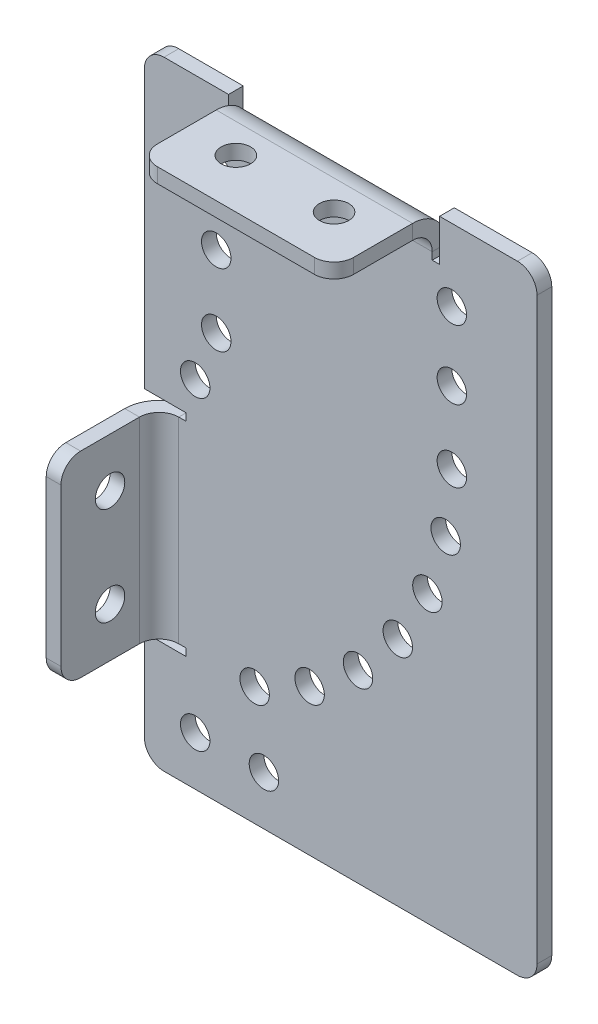
SolidWorks part; units mm, degrees
note: The reader was unsure of these and kept them because the rebuilt part matched: thickness of "基体-法兰2", "边线-法兰2", "边线-法兰3", "钣金10", "钣金11", "钣金12"; flange length of "边线-法兰2", "边线-法兰3".
ref_plane "前视基准面" through (0, 0, 0) normal (0, 0, 1) x (1, 0, 0)
ref_plane "上视基准面" through (0, 0, 0) normal (0, 1, 0) x (1, 0, 0)
ref_plane "右视基准面" through (0, 0, 0) normal (1, 0, 0) x (0, 0, -1)
other "Configuration Table"
sketch "草图1" plane through (0, 0, 0) normal (0, 0, 1) x (1, 0, 0)
  line L0 (0, 34) -> (0, 22)
  line L5 (0, 10) -> (0, 22)
  line L6 (0, 10) -> (0, 7)
  line L7 (0, 34) -> (0, 37)
  line L9 (0, 41.32) -> (0, 37)
  line L10 (0, 41.32) -> (4.32, 41.32) construction
  line L11 (7.32, 41.32) -> (4.32, 41.32) construction
  line L12 (19.32, 41.32) -> (7.32, 41.32) construction
  line L13 (19.32, 41.32) -> (31.32, 41.32) construction
  line L14 (31.32, 41.32) -> (34.32, 41.32) construction
  line L15 (0, 7) -> (0, 2)
  line L20 (4.32, 41.32) -> (4.32, 63) construction
  line L21 (4.32, 63) -> (34.32, 63)
  line L22 (34.32, 63) -> (34.32, 41.32) construction
  line L23 (0, 41.32) -> (5.176, 36.144) construction
  line L24 (5.176, 36.144) -> (5.176, 10.4307) construction
  line L25 (2, 0) -> (38, 0)
  line L30 (40, 2) -> (40, 61)
  line L31 (38, 63) -> (34.32, 63)
  line L32 (4.32, 63) -> (2, 63)
  line L33 (0, 61) -> (0, 41.32)
  line L37 (5.176, 10.4307) -> (5.176, 0) construction
  line L41 (19.32, 41.32) -> (19.32, 0) construction
  line L43 (5.176, 5) -> (12.176, 5) construction
  line L44 (7.32, 41.32) -> (7.32, 63) construction
  line L45 (31.32, 41.32) -> (31.32, 63) construction
  line L46 (7.32, 52.16) -> (31.32, 52.16) construction
  arc A0 (0, 34) -> (7.32, 41.32) centre (0, 41.32) ccw construction
  arc A1 (0, 22) -> (19.32, 41.32) centre (0, 41.32) ccw construction
  arc A2 (0, 10) -> (31.32, 41.32) centre (0, 41.32) ccw construction
  arc A3 (0, 37) -> (4.32, 41.32) centre (0, 41.32) ccw construction
  arc A4 (0, 7) -> (34.32, 41.32) centre (0, 41.32) ccw construction
  circle A6 centre (5.176, 36.144) radius 1.5
  circle A7 centre (7.32, 41.32) radius 1.5
  circle A8 centre (31.32, 41.32) radius 1.5
  circle A9 centre (30.6914, 35.0768) radius 1.5
  circle A10 centre (28.831, 29.0841) radius 1.5
  circle A11 centre (25.8133, 23.5826) radius 1.5
  circle A12 centre (21.7595, 18.793) radius 1.5
  circle A13 centre (16.8323, 14.9076) radius 1.5
  circle A14 centre (11.2295, 12.0824) radius 1.5
  circle A15 centre (5.176, 10.4307) radius 1.5 construction
  circle A16 centre (5.176, 5) radius 1.5
  circle A17 centre (12.176, 5) radius 1.5
  arc A18 (38, 0) -> (40, 2) centre (38, 2) ccw
  arc A19 (0, 2) -> (2, 0) centre (2, 2) ccw
  arc A20 (40, 61) -> (38, 63) centre (38, 61) ccw
  arc A21 (2, 63) -> (0, 61) centre (2, 61) ccw
  circle A22 centre (7.32, 55.66) radius 1.5
  circle A23 centre (7.32, 48.66) radius 1.5
  circle A24 centre (31.32, 55.66) radius 1.5
  circle A25 centre (31.32, 48.66) radius 1.5
  point P43 (40, 0)
  point P46 (0, 0)
  dimension "D7" = 3
  dimension "D12" = 3
  dimension "D13" = 2
  dimension "D16" = 3
  dimension "D1" = 3
  dimension "D2" = 24
  dimension "D3" = 19.32
  dimension "D4" = 22
  dimension "D5" = 63
  dimension "D6" = 45
  dimension "D8" = 8
  dimension "D9" = 40
  dimension "D10" = 5
  dimension "D11" = 7
  dimension "D14" = 3.5
  dimension "D15" = 3.5
  dimension "D17" = 3.5
  dimension "D18" = 3.5
base flange "基体-法兰2" sketch "草图1" thickness 1.5 reverse thickness direction no parameters "D1"=2
edge flange "边线-法兰2" sketch "草图17" flange angle 90 flange length 11.5 flange position material inside bend radius 2 thickness 1.5 parameters "D6"=10
sketch "草图17" plane through (0, 63, 0) normal (0, 1, 0) x (-1, 0, 0)
  line L1 (-29.32, 0) -> (-9.32, 0)
  line L2 (-29.32, 0) -> (-29.32, 8)
  line L3 (-27.32, 10) -> (-11.32, 10)
  line L4 (-9.32, 8) -> (-9.32, 0)
  line L5 (-19.32, 10) -> (-19.32, 0) construction
  line L6 (-38, 0) -> (-2, 0) construction
  line L7 (-29.32, 5) -> (-19.32, 5) construction
  line L8 (-19.32, 5) -> (-9.32, 5) construction
  circle A0 centre (-24.32, 5) radius 1.5
  circle A1 centre (-14.32, 5) radius 1.5
  arc A2 (-11.32, 10) -> (-9.32, 8) centre (-11.32, 8) cw
  arc A3 (-29.32, 8) -> (-27.32, 10) centre (-27.32, 8) cw
  dimension "D4" = 3
  dimension "D5" = 2
  dimension "D1" = 19.32
  dimension "D2" = 20
  dimension "D3" = 10
bend "边线折弯2" bend radius 2 bend angle 90 parameters "D5"=1
edge flange "边线-法兰3" sketch "草图20" flange angle 90 flange length 11.5 flange position material inside bend radius 2 thickness 1.5 parameters "D6"=10
sketch "草图20" plane through (0, 0, 0) normal (-1, 0, 0) x (0, -1, 0)
  line L2 (-32, 0) -> (-32, 8)
  line L3 (-30, 10) -> (-14, 10)
  line L4 (-12, 8) -> (-12, 0)
  line L5 (-61, 0) -> (-2, 0) construction
  line L6 (-22, 10) -> (-22, 0) construction
  line L7 (-32, 0) -> (-12, 0)
  line L8 (-32, 5) -> (-22, 5) construction
  line L9 (-22, 5) -> (-12, 5) construction
  circle A0 centre (-27, 5) radius 1.5
  circle A1 centre (-17, 5) radius 1.5
  arc A2 (-14, 10) -> (-12, 8) centre (-14, 8) cw
  arc A3 (-32, 8) -> (-30, 10) centre (-30, 8) cw
  point P18 (-12, 10)
  dimension "D4" = 3
  dimension "D5" = 2
  dimension "D1" = 22
  dimension "D2" = 20
  dimension "D3" = 10
bend "边线折弯3" bend radius 2 bend angle 90 parameters "D5"=2
sketch "折弯-线3" plane through (0, 0, 0) normal (0, 1, 0) x (1, 0, 0)
sketch "边界框3" plane through (0, 0, 0) normal (0, 1, 0) x (1, 0, 0)
sheet metal parameters "钣金10" thickness 1.5 parameters "D1"=2
flat pattern "平板型式10" [suppressed]
sketch "折弯-线4" plane through (0, 0, 0) normal (0, 1, 0) x (1, 0, 0)
sketch "边界框4" [suppressed] plane through (0, 0, 0) normal (0, 1, 0) x (1, 0, 0)
sheet metal parameters "钣金11" thickness 1.5 parameters "D1"=2, "D7"=2
flat pattern "平板型式10" [suppressed]
sketch "折弯-线4" plane through (0, 0, 0) normal (0, 1, 0) x (1, 0, 0)
sketch "边界框4" [suppressed] plane through (0, 0, 0) normal (0, 1, 0) x (1, 0, 0)
bend of the flat pattern "展平-<边线折弯2>1"
sheet metal parameters "钣金12" thickness 1.5 parameters "D1"=2, "D7"=2
flat pattern "平板型式10" [suppressed]
sketch "折弯-线4" plane through (0, 0, 0) normal (0, 1, 0) x (1, 0, 0)
sketch "边界框4" [suppressed] plane through (0, 0, 0) normal (0, 1, 0) x (1, 0, 0)
bend of the flat pattern "展平-<边线折弯2>1"
bend of the flat pattern "展平-<边线折弯3>1"
